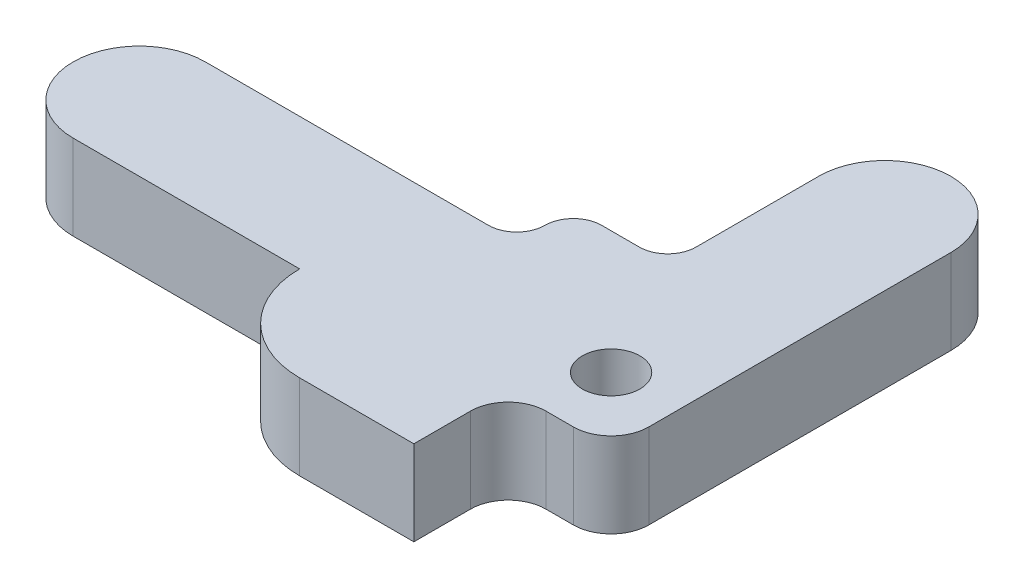
SolidWorks part; units mm, degrees
ref_plane "前视基准面" through (0, 0, 0) normal (0, 0, 1) x (1, 0, 0)
ref_plane "上视基准面" through (0, 0, 0) normal (0, 1, 0) x (1, 0, 0)
ref_plane "右视基准面" through (0, 0, 0) normal (1, 0, 0) x (0, 0, -1)
sketch "草图1" plane through (0, 0, 0) normal (0, 1, 0) x (1, 0, 0)
  line L0 (0, 0) -> (0, -8.5) construction
  line L1 (0, -8.5) -> (0, -3.5) construction
  line L2 (0, -3.5) -> (-10.0183, -3.5) construction
  line L4 (3.5, -3.5) -> (3.5, 3.5)
  line L5 (-8.5, 3.5) -> (-23.05, 3.5)
  line L6 (-23.05, 3.5) -> (-23.05, -3.5) construction
  line L7 (-1.95, -8.5) -> (-7.55, -8.5)
  line L8 (-7.55, -8.5) -> (-7.55, -3.5) construction
  line L9 (-23.05, -3.5) -> (-13, -3.5)
  line L10 (3.5, 0) -> (3.5, 18)
  line L11 (3.5, 18) -> (-3.5, 18)
  line L12 (-3.5, 18) -> (-3.5, 8.5)
  line L13 (-23.05, -3.5) -> (-28.05, -3.5)
  line L14 (-3.5, 8.5) -> (-8.5, 8.5) construction
  line L15 (-8.5, 6.5) -> (-8.5, 3.5)
  line L16 (-28.05, -3.5) -> (-28.05, 3.5) construction
  line L17 (-28.05, 3.5) -> (-23.05, 3.5)
  line L18 (-7.55, -8.5) -> (-12.55, -8.5)
  line L19 (-12.55, -8.5) -> (-12.55, -3.5) construction
  line L20 (3.5, -3.5) -> (-1.5, -3.5)
  line L21 (-1.5, -8.5) -> (-1.5, -3.5) construction
  line L22 (-3.5, 8.5) -> (-3.5, 6.95)
  line L23 (-3.5, 6.95) -> (-8.5, 6.95) construction
  line L24 (-12.55, -8.5) -> (-13, -8.5)
  line L25 (-13, -8.5) -> (-13, -3.5)
  line L26 (-28.05, -3.5) -> (-28.5, -3.5)
  line L27 (-28.5, -3.5) -> (-28.5, 3.5)
  line L28 (-28.5, 3.5) -> (-28.05, 3.5)
  line L29 (-3.5, 6.95) -> (-3.5, 6.5)
  line L30 (-3.5, 6.5) -> (-8.5, 6.5)
  line L31 (-1.95, -3.5) -> (-1.5, -3.5)
  line L32 (-1.95, -8.5) -> (-1.95, -3.5)
  circle A0 centre (0, 0) radius 1.525
  dimension "D1" = 8.5
  dimension "D2" = 5
extrude "凸台-拉伸1" add sketch "草图1" along normal blind 4.5 contours L14 L15 L5 L6 L9 L8 L7 L4 L10 L11 L12 A0 region at (-8.5031, 0, -2.1486)
sketch "草图2" plane through (0, 0, 0) normal (0, 1, 0) x (1, 0, 0)
  line L0 (-8.5, 3.5) -> (-3.5, 3.5)
  line L1 (-3.5, 3.5) -> (-3.5, 6.5)
  line L10 (-3.5, 6.5) -> (-8.5, 6.5)
  line L11 (-8.5, 6.5) -> (-8.5, 3.5)
  line L12 (-8.5, 3.5) -> (-28.5, 3.5)
  line L13 (-13, -8.5) -> (-1.95, -8.5)
  line L14 (-28.5, -3.5) -> (-13, -3.5)
  line L16 (-1.95, -8.5) -> (-1.95, -3.5)
  line L17 (3.5, -3.5) -> (3.5, 18)
  line L18 (3.5, 18) -> (-3.5, 18)
  line L19 (-3.5, 18) -> (-3.5, 6.5)
  line L21 (-8.5, 6.5) -> (-8.5, 3.5)
  line L27 (-1.95, -3.5) -> (3.5, -3.5)
  line L31 (-13, -3.5) -> (-13, -8.5)
  line L34 (-3.5, 6.5) -> (-8.5, 6.5)
  line L35 (-28.5, 3.5) -> (-28.5, -3.5)
  dimension "D1" = 0
extrude "凸台-拉伸2" add sketch "草图2" against normal blind 4
fillet "圆角1" radius 3.5 4 edges at (3.5, 2.25, -18) (-3.5, 2.25, -18) (-28.5, 2.25, 3.5) (-28.5, 2.25, -3.5)
fillet "圆角3" radius 1.5 3 edges at (-8.5, 2.25, -3.5) (-8.5, 0.25, -6.5) (-3.5, 2.25, -6.5)
fillet "圆角4" radius 5 1 edges at (-13, 2.25, 8.5)
fillet "圆角5" radius 2 2 edges at (3.5, 2.25, 3.5) (-1.95, 2.25, 3.5)
